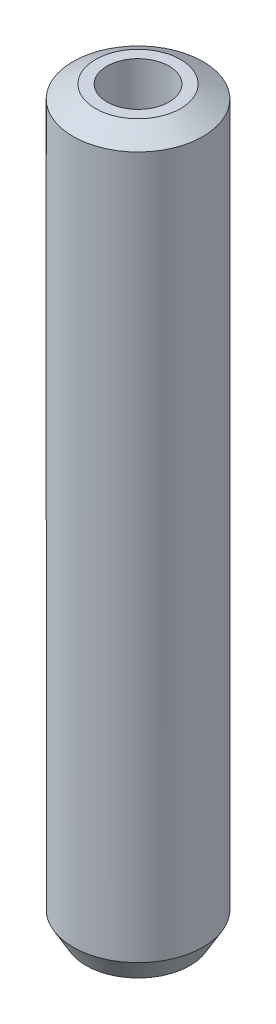
SolidWorks part; units mm, degrees
ref_plane "Front Plane" through (0, 0, 0) normal (0, 0, 1) x (1, 0, 0)
ref_plane "Top Plane" through (0, 0, 0) normal (0, 1, 0) x (1, 0, 0)
ref_plane "Right Plane" through (0, 0, 0) normal (1, 0, 0) x (0, 0, -1)
sketch "Sketch1" plane through (0, 0, 0) normal (0, 1, 0) x (1, 0, 0)
  circle A0 centre (0, 0) radius 10
  dimension "SHAFT_OD" = 20
extrude "Boss-Extrude1" add sketch "Sketch1" along normal blind 113.5024
sketch "Sketch2" plane through (0, 0, 0) normal (0, 1, 0) x (1, 0, 0)
  circle A0 centre (0, 0) radius 4.7806
  dimension "BORE_D" = 9.5612
extrude "Cut-Extrude1" cut sketch "Sketch2" along normal through all
chamfer "Chamfer1" distance 1.9943 angle 60 2 edges at (0, 113.5024, 10) (0, 0, 10) first distance on face at (0, 113.5024, 10) first distance on face at (0, 0, 4.7806)
